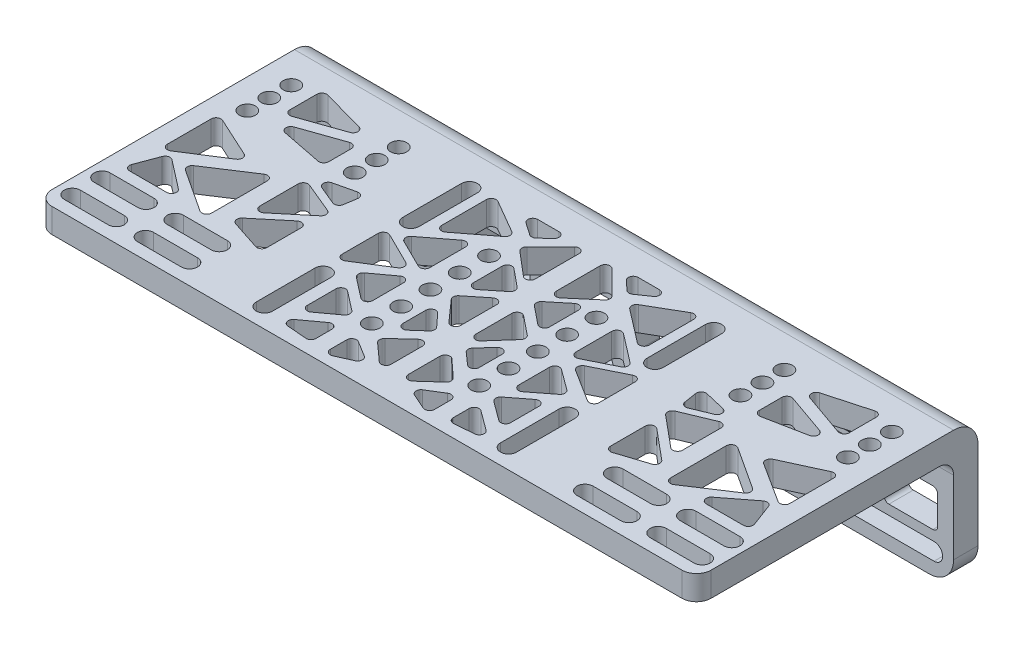
SolidWorks part; units mm, degrees
ref_plane "前视基准面" through (0, 0, 0) normal (0, 0, 1) x (1, 0, 0)
ref_plane "上视基准面" through (0, 0, 0) normal (0, 1, 0) x (1, 0, 0)
ref_plane "右视基准面" through (0, 0, 0) normal (1, 0, 0) x (0, 0, -1)
sketch "草图1" plane through (0, 0, 0) normal (0, 1, 0) x (1, 0, 0)
  line L1 (-67.5, -35) -> (67.5, -35)
  line L2 (-67.5, -35) -> (-67.5, 35)
  line L3 (-67.5, 35) -> (67.5, 35)
  line L4 (67.5, -35) -> (67.5, 35)
  line L5 (-67.5, -35) -> (67.5, 35) construction
  line L6 (-67.5, 35) -> (67.5, -35) construction
  point P0 (0, 0)
  dimension "D1" = 135
  dimension "D2" = 70
extrude "凸台-拉伸1" add sketch "草图1" along normal blind 5
sketch "草图2" plane through (0, 5, 0) normal (0, 1, 0) x (1, 0, 0)
  line L0 (-64.5, -30.85) -> (-55.5, -30.85) construction
  line L1 (-64.5, -29.2) -> (-55.5, -29.2)
  line L2 (-64.5, -32.5) -> (-55.5, -32.5)
  line L3 (-67.5, 35) -> (-67.5, -35) construction
  line L4 (-67.5, -35) -> (67.5, -35) construction
  line L5 (0, 35) -> (0, -35) construction
  line L6 (67.5, 35) -> (-67.5, 35) construction
  line L7 (-64.5, -24.75) -> (-55.5, -24.75) construction
  line L8 (-64.5, -23.1) -> (-55.5, -23.1)
  line L9 (-64.5, -26.4) -> (-55.5, -26.4)
  line L10 (64.5, -30.85) -> (55.5, -30.85) construction
  line L11 (64.5, -29.2) -> (55.5, -29.2)
  line L12 (64.5, -32.5) -> (55.5, -32.5)
  line L13 (64.5, -24.75) -> (55.5, -24.75) construction
  line L14 (64.5, -23.1) -> (55.5, -23.1)
  line L15 (64.5, -26.4) -> (55.5, -26.4)
  line L16 (-52.5, -19.5117) -> (-52.5, -34.4576) construction
  line L17 (-40.5, -30.85) -> (-49.5, -30.85) construction
  line L18 (-40.5, -29.2) -> (-49.5, -29.2)
  line L19 (-40.5, -32.5) -> (-49.5, -32.5)
  line L20 (-40.5, -24.75) -> (-49.5, -24.75) construction
  line L21 (-40.5, -23.1) -> (-49.5, -23.1)
  line L22 (-40.5, -26.4) -> (-49.5, -26.4)
  line L23 (40.5, -30.85) -> (49.5, -30.85) construction
  line L24 (40.5, -29.2) -> (49.5, -29.2)
  line L25 (40.5, -32.5) -> (49.5, -32.5)
  line L26 (40.5, -24.75) -> (49.5, -24.75) construction
  line L27 (40.5, -23.1) -> (49.5, -23.1)
  line L28 (40.5, -26.4) -> (49.5, -26.4)
  arc A0 (-64.5, -29.2) -> (-64.5, -32.5) centre (-64.5, -30.85) ccw
  arc A1 (-55.5, -32.5) -> (-55.5, -29.2) centre (-55.5, -30.85) ccw
  arc A2 (-64.5, -23.1) -> (-64.5, -26.4) centre (-64.5, -24.75) ccw
  arc A3 (-55.5, -26.4) -> (-55.5, -23.1) centre (-55.5, -24.75) ccw
  arc A4 (64.5, -29.2) -> (64.5, -32.5) centre (64.5, -30.85) cw
  arc A5 (55.5, -32.5) -> (55.5, -29.2) centre (55.5, -30.85) cw
  arc A6 (64.5, -23.1) -> (64.5, -26.4) centre (64.5, -24.75) cw
  arc A7 (55.5, -26.4) -> (55.5, -23.1) centre (55.5, -24.75) cw
  arc A8 (-40.5, -29.2) -> (-40.5, -32.5) centre (-40.5, -30.85) cw
  arc A9 (-49.5, -32.5) -> (-49.5, -29.2) centre (-49.5, -30.85) cw
  arc A10 (-40.5, -23.1) -> (-40.5, -26.4) centre (-40.5, -24.75) cw
  arc A11 (-49.5, -26.4) -> (-49.5, -23.1) centre (-49.5, -24.75) cw
  arc A12 (40.5, -29.2) -> (40.5, -32.5) centre (40.5, -30.85) ccw
  arc A13 (49.5, -32.5) -> (49.5, -29.2) centre (49.5, -30.85) ccw
  arc A14 (40.5, -23.1) -> (40.5, -26.4) centre (40.5, -24.75) ccw
  arc A15 (49.5, -26.4) -> (49.5, -23.1) centre (49.5, -24.75) ccw
  point P2 (-60, -30.85)
  point P19 (-60, -24.75)
  point P24 (60, -30.85)
  point P31 (60, -24.75)
  point P40 (-45, -30.85)
  point P47 (-45, -24.75)
  point P54 (45, -30.85)
  point P61 (45, -24.75)
  dimension "D1" = 1.65
  dimension "D2" = 3
  dimension "D3" = 2.5
  dimension "D4" = 9
  dimension "D6" = 15
  dimension "D5" = 2
extrude "切除-拉伸1" cut sketch "草图2" against normal through all
sketch "草图3" plane through (0, 5, 0) normal (0, 1, 0) x (1, 0, 0)
  line L0 (-25, 11) -> (-25, -1) construction
  line L1 (-23.35, 11) -> (-23.35, -1)
  line L2 (-26.65, 11) -> (-26.65, -1)
  line L3 (0, 35) -> (0, -35) construction
  line L4 (67.5, 35) -> (-67.5, 35) construction
  line L5 (-67.5, -35) -> (67.5, -35) construction
  line L6 (25, 11) -> (25, -1) construction
  line L7 (23.35, 11) -> (23.35, -1)
  line L8 (26.65, 11) -> (26.65, -1)
  line L9 (-25, 5) -> (25, 5) construction
  line L10 (-25, -19) -> (-25, -31) construction
  line L11 (-23.35, -19) -> (-23.35, -31)
  line L12 (-26.65, -19) -> (-26.65, -31)
  line L13 (25, -19) -> (25, -31) construction
  line L14 (23.35, -19) -> (23.35, -31)
  line L15 (26.65, -19) -> (26.65, -31)
  line L16 (-25, -25) -> (25, -25) construction
  arc A0 (-23.35, 11) -> (-26.65, 11) centre (-25, 11) ccw
  arc A1 (-26.65, -1) -> (-23.35, -1) centre (-25, -1) ccw
  arc A2 (23.35, 11) -> (26.65, 11) centre (25, 11) cw
  arc A3 (26.65, -1) -> (23.35, -1) centre (25, -1) cw
  arc A4 (-23.35, -19) -> (-26.65, -19) centre (-25, -19) ccw
  arc A5 (-26.65, -31) -> (-23.35, -31) centre (-25, -31) ccw
  arc A6 (23.35, -19) -> (26.65, -19) centre (25, -19) cw
  arc A7 (26.65, -31) -> (23.35, -31) centre (25, -31) cw
  point P2 (-25, 5)
  point P15 (25, 5)
  point P24 (-25, -25)
  point P31 (25, -25)
  dimension "D4" = 1.65
  dimension "D5" = 1.65
  dimension "D1" = 50
  dimension "D2" = 24
  dimension "D3" = 12
  dimension "D6" = 4
  dimension "D7" = 12
extrude "切除-拉伸2" cut sketch "草图3" against normal through all
sketch "草图4" plane through (0, 5, 0) normal (0, 1, 0) x (1, 0, 0)
  line L0 (0, 35) -> (0, -35) construction
  line L1 (67.5, 35) -> (-67.5, 35) construction
  line L2 (-67.5, -35) -> (67.5, -35) construction
  circle A0 centre (-11, 1) radius 1.65
  circle A1 centre (11, 1) radius 1.65
  circle A2 centre (-11, -5) radius 1.65
  circle A3 centre (11, -5) radius 1.65
  circle A4 centre (-11, -11) radius 1.65
  circle A5 centre (11, -11) radius 1.65
  circle A6 centre (-11, -17) radius 1.65
  circle A7 centre (11, -17) radius 1.65
  circle A8 centre (-11, -23) radius 1.65
  circle A9 centre (11, -23) radius 1.65
  dimension "D1" = 3.3
  dimension "D2" = 22
  dimension "D3" = 34
  dimension "D4" = 5
extrude "切除-拉伸3" cut sketch "草图4" against normal through all
sketch "草图12" plane through (0, 5, 0) normal (0, 1, 0) x (1, 0, 0)
  line L0 (-63.7341, -3.1683) -> (-63.7341, -12.1456)
  line L1 (-62.1953, -12.9881) -> (-54.0246, -7.763)
  line L2 (-54.146, -6.0118) -> (-62.3167, -2.2596)
  line L3 (-57.2351, -13.2541) -> (-48.5324, -7.5705)
  line L4 (-46.9856, -8.4078) -> (-46.9856, -19.824)
  line L5 (-48.5357, -20.6591) -> (-57.2384, -14.9265)
  line L6 (-60.5319, -14.412) -> (-54.6423, -18.9715)
  line L7 (-55.2545, -20.7622) -> (-62.8532, -20.7622)
  line L8 (-63.7895, -19.4112) -> (-62.0804, -14.8518)
  line L30 (-43.298, -5.7806) -> (-43.298, -13.6622)
  line L31 (-41.6579, -14.4305) -> (-35.3502, -9.1761)
  line L32 (-35.6058, -7.4847) -> (-41.9135, -4.8574)
  line L33 (-40.1945, -4.0399) -> (-36.3747, -5.6308)
  line L34 (-35.0024, -4.8633) -> (-34.5948, -2.2755)
  line L35 (-35.8121, -1.1466) -> (-40.0395, -2.1434)
  line L36 (-42.9398, -17.5571) -> (-36.8405, -12.4762)
  line L37 (-35.2004, -13.2445) -> (-35.2004, -20.3144)
  line L38 (-36.5104, -21.2652) -> (-42.6098, -19.2761)
  line L39 (0, 35) -> (0, -35) construction
  line L40 (67.5, 35) -> (-67.5, 35) construction
  line L41 (-67.5, -35) -> (67.5, -35) construction
  arc A15 (-36.3747, -5.6308) -> (-35.0024, -4.8633) centre (-35.9903, -4.7077) ccw
  arc A16 (-34.5948, -2.2755) -> (-35.8121, -1.1466) centre (-35.5826, -2.1199) ccw
  arc A17 (-40.0395, -2.1434) -> (-40.1945, -4.0399) centre (-39.81, -3.1167) ccw
  arc A18 (-35.3502, -9.1761) -> (-35.6058, -7.4847) centre (-35.9903, -8.4078) ccw
  arc A19 (-41.9135, -4.8574) -> (-43.298, -5.7806) centre (-42.298, -5.7806) ccw
  arc A20 (-43.298, -13.6622) -> (-41.6579, -14.4305) centre (-42.298, -13.6622) ccw
  arc A21 (-36.8405, -12.4762) -> (-35.2004, -13.2445) centre (-36.2004, -13.2445) cw
  arc A22 (-35.2004, -20.3144) -> (-36.5104, -21.2652) centre (-36.2004, -20.3144) cw
  arc A23 (-42.6098, -19.2761) -> (-42.9398, -17.5571) centre (-42.2998, -18.3254) cw
  arc A24 (-48.5357, -20.6591) -> (-46.9856, -19.824) centre (-47.9856, -19.824) ccw
  arc A25 (-46.9856, -8.4078) -> (-48.5324, -7.5705) centre (-47.9856, -8.4078) ccw
  arc A26 (-57.2351, -13.2541) -> (-57.2384, -14.9265) centre (-56.6883, -14.0914) ccw
  arc A27 (-55.2545, -20.7622) -> (-54.6423, -18.9715) centre (-55.2545, -19.7622) ccw
  arc A28 (-62.8532, -20.7622) -> (-63.7895, -19.4112) centre (-62.8532, -19.7622) cw
  arc A29 (-62.0804, -14.8518) -> (-60.5319, -14.412) centre (-61.144, -15.2028) cw
  arc A30 (-54.146, -6.0118) -> (-54.0246, -7.763) centre (-54.5634, -6.9206) cw
  arc A31 (-62.1953, -12.9881) -> (-63.7341, -12.1456) centre (-62.7341, -12.1456) cw
  arc A32 (-63.7341, -3.1683) -> (-62.3167, -2.2596) centre (-62.7341, -3.1683) cw
extrude "切除-拉伸8" cut sketch "草图12" against normal through all
sketch "草图13" plane through (0, 5, 0) normal (0, 1, 0) x (1, 0, 0)
  line L0 (-26.3284, -6.3566) -> (-26.3284, -13.7782)
  line L1 (-24.7954, -14.6243) -> (-18.2042, -10.4723)
  line L2 (-18.2928, -8.7304) -> (-24.884, -5.4607)
  line L3 (-22.2153, -5.1856) -> (-16.4065, -8.0671)
  line L4 (-14.9622, -7.1713) -> (-14.9622, 0.1753)
  line L5 (-16.5716, 0.9681) -> (-22.3803, -3.497)
  line L6 (-19.634, 0.7521) -> (-12.8519, 5.9654)
  line L7 (-12.9589, 7.6229) -> (-19.741, 11.5638)
  line L8 (-21.2435, 10.6991) -> (-21.2435, 1.5449)
  line L9 (-20.7454, -14.8066) -> (-16.5546, -11.725)
  line L10 (-14.9622, -12.5307) -> (-14.9622, -18.8711)
  line L11 (-16.576, -19.6605) -> (-20.7669, -16.4017)
  line L12 (-19.2026, -19.7572) -> (-15.3324, -22.7666)
  line L13 (-15.3539, -24.3617) -> (-19.224, -27.2074)
  line L14 (-20.8164, -26.4017) -> (-20.8164, -20.5466)
  line L15 (-19.6599, -30.255) -> (-15.6493, -27.306)
  line L16 (-14.0569, -28.1117) -> (-14.0569, -31.3933)
  line L17 (-15.1396, -32.3899) -> (-19.1502, -32.0572)
  line L18 (-12.4686, 12.4368) -> (-8.1041, 12.4368)
  line L19 (-7.4241, 10.7035) -> (-9.2906, 8.9726)
  line L20 (-13.0382, 10.6148) -> (-10.5402, 8.8838)
  line L21 (-8.7288, 6.4582) -> (-3.8639, 11.3231)
  line L22 (-2.1568, 10.616) -> (-2.1568, 1.616)
  line L23 (-3.8045, 0.8541) -> (-8.6693, 4.9892)
  line L24 (-6.1824, 1.291) -> (-2.5396, -1.7035)
  line L25 (-2.5475, -3.2549) -> (-6.1903, -6.1876)
  line L26 (-7.8174, -5.4087) -> (-7.8174, 0.5185)
  line L27 (-7.0005, -9.1681) -> (-3.1746, -6.088)
  line L28 (-1.5475, -6.867) -> (-1.5475, -14.2616)
  line L29 (-3.2957, -14.925) -> (-7.1216, -10.6105)
  line L30 (-7.8174, -15.1154) -> (-7.8174, -19.8023)
  line L31 (-6.1539, -20.5505) -> (-3.776, -18.4419)
  line L32 (-3.7044, -17.0157) -> (-6.0823, -14.4374)
  line L33 (-7.0118, -24.3399) -> (-3.4637, -21.0675)
  line L34 (-1.7858, -21.8026) -> (-1.7858, -28.2781)
  line L35 (-3.4559, -29.0204) -> (-7.0039, -25.8172)
  line L36 (-10.6733, -28.4621) -> (-10.6733, -31.8412)
  line L37 (-9.2648, -32.754) -> (-6.0857, -31.3312)
  line L38 (-5.9701, -29.5668) -> (-9.1492, -27.6104)
  arc A0 (-7.4241, 10.7035) -> (-8.1041, 12.4368) centre (-8.1041, 11.4368) ccw
  arc A1 (-12.4686, 12.4368) -> (-13.0382, 10.6148) centre (-12.4686, 11.4368) ccw
  arc A2 (-10.5402, 8.8838) -> (-9.2906, 8.9726) centre (-9.9706, 9.7058) ccw
  arc A3 (-3.8045, 0.8541) -> (-2.1568, 1.616) centre (-3.1568, 1.616) ccw
  arc A4 (-2.1568, 10.616) -> (-3.8639, 11.3231) centre (-3.1568, 10.616) ccw
  arc A5 (-8.7288, 6.4582) -> (-8.6693, 4.9892) centre (-8.0216, 5.7511) ccw
  arc A6 (-2.5475, -3.2549) -> (-2.5396, -1.7035) centre (-3.1746, -2.4759) ccw
  arc A7 (-6.1824, 1.291) -> (-7.8174, 0.5185) centre (-6.8174, 0.5185) ccw
  arc A8 (-7.8174, -5.4087) -> (-6.1903, -6.1876) centre (-6.8174, -5.4087) ccw
  arc A9 (-1.5475, -6.867) -> (-3.1746, -6.088) centre (-2.5475, -6.867) ccw
  arc A10 (-7.0005, -9.1681) -> (-7.1216, -10.6105) centre (-6.3733, -9.9471) ccw
  arc A11 (-3.2957, -14.925) -> (-1.5475, -14.2616) centre (-2.5475, -14.2616) ccw
  arc A12 (-3.776, -18.4419) -> (-3.7044, -17.0157) centre (-4.4395, -17.6937) ccw
  arc A13 (-6.0823, -14.4374) -> (-7.8174, -15.1154) centre (-6.8174, -15.1154) ccw
  arc A14 (-7.8174, -19.8023) -> (-6.1539, -20.5505) centre (-6.8174, -19.8023) ccw
  arc A15 (-3.4559, -29.0204) -> (-1.7858, -28.2781) centre (-2.7858, -28.2781) ccw
  arc A16 (-1.7858, -21.8026) -> (-3.4637, -21.0675) centre (-2.7858, -21.8026) ccw
  arc A17 (-7.0118, -24.3399) -> (-7.0039, -25.8172) centre (-6.3338, -25.075) ccw
  arc A18 (-10.6733, -31.8412) -> (-9.2648, -32.754) centre (-9.6733, -31.8412) ccw
  arc A19 (-6.0857, -31.3312) -> (-5.9701, -29.5668) centre (-6.4942, -30.4184) ccw
  arc A20 (-9.1492, -27.6104) -> (-10.6733, -28.4621) centre (-9.6733, -28.4621) ccw
  arc A21 (-15.6493, -27.306) -> (-14.0569, -28.1117) centre (-15.0569, -28.1117) cw
  arc A22 (-14.0569, -31.3933) -> (-15.1396, -32.3899) centre (-15.0569, -31.3933) cw
  arc A23 (-19.1502, -32.0572) -> (-19.6599, -30.255) centre (-19.0675, -31.0606) cw
  arc A24 (-15.3324, -22.7666) -> (-15.3539, -24.3617) centre (-15.9463, -23.556) cw
  arc A25 (-19.224, -27.2074) -> (-20.8164, -26.4017) centre (-19.8164, -26.4017) cw
  arc A26 (-20.8164, -20.5466) -> (-19.2026, -19.7572) centre (-19.8164, -20.5466) cw
  arc A27 (-16.576, -19.6605) -> (-14.9622, -18.8711) centre (-15.9622, -18.8711) ccw
  arc A28 (-14.9622, -12.5307) -> (-16.5546, -11.725) centre (-15.9622, -12.5307) ccw
  arc A29 (-20.7454, -14.8066) -> (-20.7669, -16.4017) centre (-20.153, -15.6122) ccw
  arc A30 (-18.2928, -8.7304) -> (-18.2042, -10.4723) centre (-18.7372, -9.6262) cw
  arc A31 (-24.7954, -14.6243) -> (-26.3284, -13.7782) centre (-25.3284, -13.7782) cw
  arc A32 (-26.3284, -6.3566) -> (-24.884, -5.4607) centre (-25.3284, -6.3566) cw
  arc A33 (-16.5716, 0.9681) -> (-14.9622, 0.1753) centre (-15.9622, 0.1753) cw
  arc A34 (-14.9622, -7.1713) -> (-16.4065, -8.0671) centre (-15.9622, -7.1713) cw
  arc A35 (-22.2153, -5.1856) -> (-22.3803, -3.497) centre (-21.7709, -4.2898) cw
  arc A36 (-21.2435, 1.5449) -> (-19.634, 0.7521) centre (-20.2435, 1.5449) ccw
  arc A37 (-12.8519, 5.9654) -> (-12.9589, 7.6229) centre (-13.4613, 6.7582) ccw
  arc A38 (-19.741, 11.5638) -> (-21.2435, 10.6991) centre (-20.2435, 10.6991) ccw
  point P61 (-7.8174, -9.8258)
  point P118 (-21.2435, 12.4368)
  dimension "D1" = 1
extrude "切除-拉伸9" cut sketch "草图13" against normal through all
mirror "镜向1" about plane through (0, 0, 0) normal (1, 0, 0) of "切除-拉伸9", "切除-拉伸8"
sketch "草图14" plane through (0, 5, 0) normal (0, 1, 0) x (1, 0, 0)
  line L0 (-61.5, 11) -> (-39.5, 11) construction
  line L1 (-67.5, 35) -> (-67.5, -35) construction
  line L2 (67.5, 35) -> (-67.5, 35) construction
  line L3 (0, 35) -> (0, -35) construction
  line L4 (-67.5, -35) -> (67.5, -35) construction
  circle A0 centre (-61.5, 11) radius 1.65
  circle A1 centre (-39.5, 11) radius 1.65
  circle A2 centre (39.5, 11) radius 1.65
  circle A3 centre (61.5, 11) radius 1.65
  circle A4 centre (-61.5, 6.5) radius 1.65
  circle A5 centre (-39.5, 6.5) radius 1.65
  circle A6 centre (39.5, 6.5) radius 1.65
  circle A7 centre (61.5, 6.5) radius 1.65
  circle A8 centre (-61.5, 2) radius 1.65
  circle A9 centre (-39.5, 2) radius 1.65
  circle A10 centre (39.5, 2) radius 1.65
  circle A11 centre (61.5, 2) radius 1.65
  dimension "D1" = 3.3
  dimension "D2" = 3.3
  dimension "D3" = 22
  dimension "D4" = 6
  dimension "D5" = 24
  dimension "D6" = 3
extrude "切除-拉伸11" cut sketch "草图14" against normal through all
sketch "草图15" plane through (0, 5, 0) normal (0, 1, 0) x (1, 0, 0)
  line L0 (-57.285, 12.0334) -> (-57.285, 6.4775)
  line L1 (-55.9539, 5.5339) -> (-47.105, 8.6393)
  line L2 (-47.1692, 10.5466) -> (-56.0181, 12.9971)
  line L3 (-53.8397, 3.8716) -> (-45.4266, 6.8239)
  line L4 (-44.0955, 5.8803) -> (-44.0955, 1.2618)
  line L5 (-45.2898, 0.2809) -> (-53.7029, 1.947)
  arc A0 (-45.2898, 0.2809) -> (-44.0955, 1.2618) centre (-45.0955, 1.2618) ccw
  arc A1 (-44.0955, 5.8803) -> (-45.4266, 6.8239) centre (-45.0955, 5.8803) ccw
  arc A2 (-53.8397, 3.8716) -> (-53.7029, 1.947) centre (-53.5086, 2.928) ccw
  arc A3 (-57.285, 6.4775) -> (-55.9539, 5.5339) centre (-56.285, 6.4775) ccw
  arc A4 (-47.105, 8.6393) -> (-47.1692, 10.5466) centre (-47.4361, 9.5828) ccw
  arc A5 (-56.0181, 12.9971) -> (-57.285, 12.0334) centre (-56.285, 12.0334) ccw
  dimension "D1" = 1
extrude "切除-拉伸12" cut sketch "草图15" against normal through all
mirror "镜向2" about plane through (0, 0, 0) normal (1, 0, 0) of "切除-拉伸12", "切除-拉伸11"
fillet "圆角1" radius 3 2 edges at (67.5, 2.5, 35) (-67.5, 2.5, 35)
sketch "草图16" plane through (0, 0, 0) normal (0, -1, 0) x (1, 0, 0)
  line L0 (-67.5, -35) -> (-67.5, 32) construction
  line L1 (67.5, 32) -> (67.5, -35) construction
  line L2 (-67.5, -22.65) -> (67.5, -22.65)
  line L3 (-67.5, -22.65) -> (-67.5, -17.65)
  line L4 (-67.5, -17.65) -> (67.5, -17.65)
  line L5 (67.5, -22.65) -> (67.5, -17.65)
  line L6 (-67.5, -22.65) -> (67.5, -17.65) construction
  line L7 (-67.5, -17.65) -> (67.5, -22.65) construction
  arc A0 (-26.65, -11) -> (-23.35, -11) centre (-25, -11) ccw construction
  point P0 (0, -20.15)
  point P8 (-25, -12.65)
  dimension "D1" = 5
  dimension "D2" = 5
extrude "凸台-拉伸2" add sketch "草图16" along normal blind 23
sketch "草图17" plane through (0, 0, 0) normal (0, -1, 0) x (1, 0, 0)
  line L1 (-67.5, -35) -> (67.5, -35)
  line L2 (-67.5, -35) -> (-67.5, -22.65)
  line L3 (-67.5, -22.65) -> (67.5, -22.65)
  line L4 (67.5, -35) -> (67.5, -22.65)
extrude "切除-拉伸13" cut sketch "草图17" against normal through all
fillet "圆角2" radius 5 1 edges at (0, 5, -22.65)
sketch "草图19" plane through (0, 0, 0) normal (1, 0, 0) x (0, 0, -1)
  line L0 (12.65, 0) -> (17.65, -6)
  line L1 (-32, 0) -> (17.65, 0) construction
  line L2 (17.65, -23) -> (17.65, 0) construction
  dimension "D1" = 5
  dimension "D2" = 6
rib "筋3" sketch "草图19" sketch "草图19" thickness 2 extrusion direction parallel to sketch draft on no parameters "D1"=2
pattern_linear "阵列(线性)1" count 3 spacing 23 along (1, 0, 0) of "筋3"
pattern_linear "阵列(线性)2" count 3 spacing 23 along (-1, 0, 0) of "筋3"
sketch "草图20" plane through (0, 0, -22.65) normal (0, 0, -1) x (-1, 0, 0)
  line L0 (-63.5, -18.5) -> (-41.5, -18.5) construction
  line L1 (-63.5, -16.75) -> (-41.5, -16.75)
  line L2 (-63.5, -20.25) -> (-41.5, -20.25)
  line L3 (-67.5, 5) -> (67.5, 5) construction
  line L4 (-67.5, -23) -> (-67.5, 0) construction
  line L5 (0, 5) -> (0, -23) construction
  line L6 (67.5, -23) -> (-67.5, -23) construction
  line L7 (-26, -18.5) -> (-4, -18.5) construction
  line L8 (-26, -16.75) -> (-4, -16.75)
  line L9 (-26, -20.25) -> (-4, -20.25)
  line L10 (63.5, -18.5) -> (41.5, -18.5) construction
  line L11 (63.5, -16.75) -> (41.5, -16.75)
  line L12 (63.5, -20.25) -> (41.5, -20.25)
  line L13 (26, -18.5) -> (4, -18.5) construction
  line L14 (26, -16.75) -> (4, -16.75)
  line L15 (26, -20.25) -> (4, -20.25)
  arc A0 (-63.5, -16.75) -> (-63.5, -20.25) centre (-63.5, -18.5) ccw
  arc A1 (-41.5, -20.25) -> (-41.5, -16.75) centre (-41.5, -18.5) ccw
  arc A2 (-26, -16.75) -> (-26, -20.25) centre (-26, -18.5) ccw
  arc A3 (-4, -20.25) -> (-4, -16.75) centre (-4, -18.5) ccw
  arc A4 (63.5, -16.75) -> (63.5, -20.25) centre (63.5, -18.5) cw
  arc A5 (41.5, -20.25) -> (41.5, -16.75) centre (41.5, -18.5) cw
  arc A6 (26, -16.75) -> (26, -20.25) centre (26, -18.5) cw
  arc A7 (4, -20.25) -> (4, -16.75) centre (4, -18.5) cw
  point P2 (-52.5, -18.5)
  point P17 (-15, -18.5)
  point P24 (52.5, -18.5)
  point P31 (15, -18.5)
  dimension "D1" = 1.75
  dimension "D5" = 1.75
  dimension "D2" = 23.5
  dimension "D3" = 22
  dimension "D4" = 4
  dimension "D6" = 22
  dimension "D7" = 4
extrude "切除-拉伸14" cut sketch "草图20" against normal through all
fillet "圆角4" radius 5 2 edges at (-67.5, -23, -20.15) (67.5, -23, -20.15)
fillet "圆角5" radius 3 6 edges at (57.25, 0, -17.65) (34.5, 0, -17.65) (11.5, 0, -17.65) (-11.5, 0, -17.65) (-34.5, 0, -17.65) (-57.25, 0, -17.65)
sketch "草图23" plane through (0, 0, -22.65) normal (0, 0, -1) x (-1, 0, 0)
  line L0 (0, 5) -> (0, -23) construction
  line L1 (-67.5, 5) -> (67.5, 5) construction
  line L2 (62.5, -23) -> (-62.5, -23) construction
  line L3 (-24, -6) -> (-22, -6) construction
  line L4 (-3.25, -7) -> (-12.25, -7)
  line L5 (-2.25, -8) -> (-2.25, -13.75)
  line L6 (-3.25, -14.75) -> (-12.25, -14.75)
  line L7 (-13.25, -8) -> (-13.25, -13.75)
  line L8 (-20.25, -7) -> (-29.25, -7)
  line L9 (-19.25, -8) -> (-19.25, -13.75)
  line L10 (-20.25, -14.75) -> (-29.25, -14.75)
  line L11 (-30.25, -8) -> (-30.25, -13.75)
  line L12 (-37.25, -7) -> (-46.25, -7)
  line L13 (-36.25, -8) -> (-36.25, -13.75)
  line L14 (-37.25, -14.75) -> (-46.25, -14.75)
  line L15 (-47.25, -8) -> (-47.25, -13.75)
  line L16 (-54.25, -7) -> (-63.25, -7)
  line L17 (-53.25, -8) -> (-53.25, -13.75)
  line L18 (-54.25, -14.75) -> (-63.25, -14.75)
  line L19 (-64.25, -8) -> (-64.25, -13.75)
  line L20 (64.25, -8) -> (64.25, -13.75)
  line L21 (54.25, -14.75) -> (63.25, -14.75)
  line L22 (53.25, -8) -> (53.25, -13.75)
  line L23 (54.25, -7) -> (63.25, -7)
  line L24 (47.25, -8) -> (47.25, -13.75)
  line L25 (37.25, -14.75) -> (46.25, -14.75)
  line L26 (36.25, -8) -> (36.25, -13.75)
  line L27 (37.25, -7) -> (46.25, -7)
  line L28 (30.25, -8) -> (30.25, -13.75)
  line L29 (20.25, -14.75) -> (29.25, -14.75)
  line L30 (19.25, -8) -> (19.25, -13.75)
  line L31 (20.25, -7) -> (29.25, -7)
  line L32 (13.25, -8) -> (13.25, -13.75)
  line L33 (3.25, -14.75) -> (12.25, -14.75)
  line L34 (2.25, -8) -> (2.25, -13.75)
  line L35 (3.25, -7) -> (12.25, -7)
  arc A0 (-13.25, -13.75) -> (-12.25, -14.75) centre (-12.25, -13.75) ccw
  arc A1 (-3.25, -14.75) -> (-2.25, -13.75) centre (-3.25, -13.75) ccw
  arc A2 (-4, -20.25) -> (-4, -16.75) centre (-4, -18.5) ccw construction
  arc A3 (-2.25, -8) -> (-3.25, -7) centre (-3.25, -8) ccw
  arc A4 (-12.25, -7) -> (-13.25, -8) centre (-12.25, -8) ccw
  arc A5 (-30.25, -13.75) -> (-29.25, -14.75) centre (-29.25, -13.75) ccw
  arc A6 (-20.25, -14.75) -> (-19.25, -13.75) centre (-20.25, -13.75) ccw
  arc A7 (-19.25, -8) -> (-20.25, -7) centre (-20.25, -8) ccw
  arc A8 (-29.25, -7) -> (-30.25, -8) centre (-29.25, -8) ccw
  arc A9 (-47.25, -13.75) -> (-46.25, -14.75) centre (-46.25, -13.75) ccw
  arc A10 (-37.25, -14.75) -> (-36.25, -13.75) centre (-37.25, -13.75) ccw
  arc A11 (-36.25, -8) -> (-37.25, -7) centre (-37.25, -8) ccw
  arc A12 (-46.25, -7) -> (-47.25, -8) centre (-46.25, -8) ccw
  arc A13 (-64.25, -13.75) -> (-63.25, -14.75) centre (-63.25, -13.75) ccw
  arc A14 (-54.25, -14.75) -> (-53.25, -13.75) centre (-54.25, -13.75) ccw
  arc A15 (-53.25, -8) -> (-54.25, -7) centre (-54.25, -8) ccw
  arc A16 (-63.25, -7) -> (-64.25, -8) centre (-63.25, -8) ccw
  arc A17 (63.25, -7) -> (64.25, -8) centre (63.25, -8) cw
  arc A18 (53.25, -8) -> (54.25, -7) centre (54.25, -8) cw
  arc A19 (54.25, -14.75) -> (53.25, -13.75) centre (54.25, -13.75) cw
  arc A20 (64.25, -13.75) -> (63.25, -14.75) centre (63.25, -13.75) cw
  arc A21 (46.25, -7) -> (47.25, -8) centre (46.25, -8) cw
  arc A22 (36.25, -8) -> (37.25, -7) centre (37.25, -8) cw
  arc A23 (37.25, -14.75) -> (36.25, -13.75) centre (37.25, -13.75) cw
  arc A24 (47.25, -13.75) -> (46.25, -14.75) centre (46.25, -13.75) cw
  arc A25 (29.25, -7) -> (30.25, -8) centre (29.25, -8) cw
  arc A26 (19.25, -8) -> (20.25, -7) centre (20.25, -8) cw
  arc A27 (20.25, -14.75) -> (19.25, -13.75) centre (20.25, -13.75) cw
  arc A28 (30.25, -13.75) -> (29.25, -14.75) centre (29.25, -13.75) cw
  arc A29 (12.25, -7) -> (13.25, -8) centre (12.25, -8) cw
  arc A30 (2.25, -8) -> (3.25, -7) centre (3.25, -8) cw
  arc A31 (3.25, -14.75) -> (2.25, -13.75) centre (3.25, -13.75) cw
  arc A32 (13.25, -13.75) -> (12.25, -14.75) centre (12.25, -13.75) cw
  point P22 (-2.25, -7)
  point P25 (-13.25, -7)
  point P110 (13.25, -7)
  point P111 (2.25, -7)
  dimension "D4" = 1
  dimension "D1" = 1
  dimension "D2" = 11
  dimension "D3" = 2
  dimension "D6" = 6
  dimension "D5" = 4
extrude "切除-拉伸17" cut sketch "草图23" against normal through all
